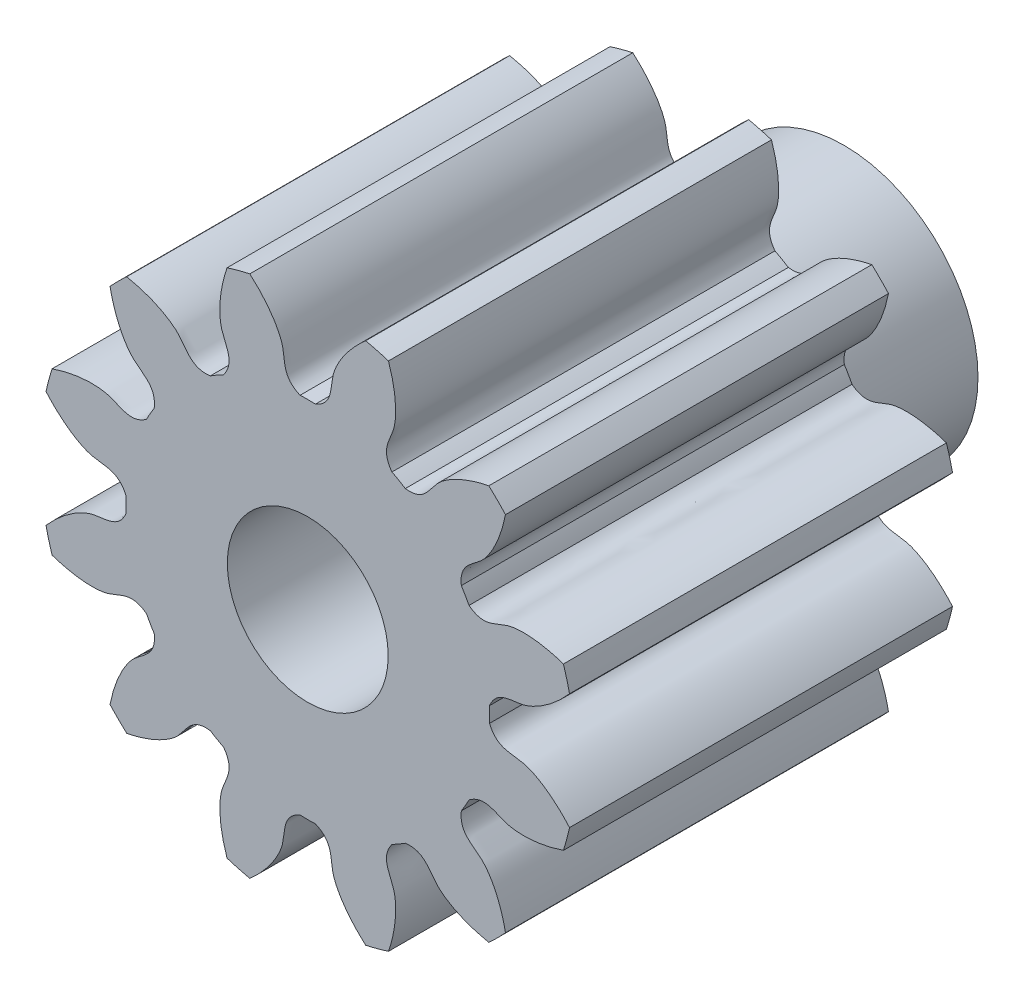
SolidWorks part; units mm, degrees
ref_plane "前视基准面" through (0, 0, 0) normal (0, 0, 1) x (1, 0, 0)
ref_plane "上视基准面" through (0, 0, 0) normal (0, 1, 0) x (1, 0, 0)
ref_plane "右视基准面" through (0, 0, 0) normal (1, 0, 0) x (0, 0, -1)
other "Configuration Table"
sketch "草图1" plane through (0, 0, 0) normal (0, 0, 1) x (1, 0, 0)
  circle A0 centre (0, 0) radius 3.5
extrude "凸台-拉伸1" add sketch "草图1" along normal blind 5
ref_axis "基准轴1" through (0, 0, 5) along (0, 0, -1)
sketch "草图2" plane through (0, 0, 0) normal (0, 0, 1) x (1, 0, 0)
  line L0 (0, 0) -> (0, 3.5) construction
  circle A0 centre (0, 0) radius 3.5 construction
  arc A1 (0.1004, 2.3729) -> (-0.1004, 2.3729) centre (0, 0) ccw
  arc A2 (1.7488, 3.9475) -> (-1.7488, 3.9475) centre (0, 0) ccw
  spline S0 degree 3 poles (0.1004, 2.3729) (0.3404, 2.4747) (0.2872, 2.6724) (0.3381, 2.8447) (0.3413, 2.855) (0.3451, 2.8662) (0.3495, 2.8784) (0.3546, 2.8915) (0.3603, 2.9056) (0.3668, 2.9206) (0.374, 2.9366) (0.3821, 2.9533) (0.3909, 2.971) (0.4007, 2.9894) (0.4114, 3.0086) (0.423, 3.0286) (0.4356, 3.0493) (0.4492, 3.0707) (0.4639, 3.0928) (0.4796, 3.1155) (0.4965, 3.1388) (0.5145, 3.1626) (0.5337, 3.187) (0.554, 3.2119) (0.5756, 3.2372) (0.5985, 3.2629) (0.6226, 3.289) (0.648, 3.3154) (0.6748, 3.342) (0.7028, 3.369) (0.7323, 3.3961) (0.7631, 3.4234) (0.7954, 3.4507) (0.829, 3.4782) (0.8641, 3.5057) (0.9006, 3.5331) (0.9385, 3.5604) (0.978, 3.5877) (1.0189, 3.6147) (1.0613, 3.6416) (1.1052, 3.6681) (1.1506, 3.6944) (1.1975, 3.7203) (1.2459, 3.7457) (1.2958, 3.7707) (1.3472, 3.7952) (1.4001, 3.8191) (1.4546, 3.8424) (1.5105, 3.865) (1.5679, 3.8869) (1.6472, 3.9154) (1.7078, 3.9351) (1.7488, 3.9475) knots 0 0 0 0 0.218015 0.222044 0.226546 0.231522 0.236972 0.242897 0.249295 0.256167 0.263513 0.271332 0.279626 0.288394 0.297636 0.307351 0.317541 0.328204 0.339341 0.350953 0.363038 0.375597 0.38863 0.402137 0.416118 0.430573 0.445502 0.460904 0.476781 0.493132 0.509956 0.527255 0.545027 0.563273 0.581994 0.601188 0.620856 0.640998 0.661614 0.682704 0.704268 0.726305 0.748817 0.771803 0.795262 0.819196 0.843603 0.868484 0.89384 0.919669 0.945972 1 1 1 1
  spline S1 degree 3 poles (-0.1004, 2.3729) (-0.3404, 2.4747) (-0.2872, 2.6724) (-0.3381, 2.8447) (-0.3413, 2.855) (-0.3451, 2.8662) (-0.3495, 2.8784) (-0.3546, 2.8915) (-0.3603, 2.9056) (-0.3668, 2.9206) (-0.374, 2.9366) (-0.3821, 2.9533) (-0.3909, 2.971) (-0.4007, 2.9894) (-0.4114, 3.0086) (-0.423, 3.0286) (-0.4356, 3.0493) (-0.4492, 3.0707) (-0.4639, 3.0928) (-0.4796, 3.1155) (-0.4965, 3.1388) (-0.5145, 3.1626) (-0.5337, 3.187) (-0.554, 3.2119) (-0.5756, 3.2372) (-0.5985, 3.2629) (-0.6226, 3.289) (-0.648, 3.3154) (-0.6748, 3.342) (-0.7028, 3.369) (-0.7323, 3.3961) (-0.7631, 3.4234) (-0.7954, 3.4507) (-0.829, 3.4782) (-0.8641, 3.5057) (-0.9006, 3.5331) (-0.9385, 3.5604) (-0.978, 3.5877) (-1.0189, 3.6147) (-1.0613, 3.6416) (-1.1052, 3.6681) (-1.1506, 3.6944) (-1.1975, 3.7203) (-1.2459, 3.7457) (-1.2958, 3.7707) (-1.3472, 3.7952) (-1.4001, 3.8191) (-1.4546, 3.8424) (-1.5105, 3.865) (-1.5679, 3.8869) (-1.6472, 3.9154) (-1.7078, 3.9351) (-1.7488, 3.9475) knots 0 0 0 0 0.218015 0.222044 0.226546 0.231522 0.236972 0.242897 0.249295 0.256167 0.263513 0.271332 0.279626 0.288394 0.297636 0.307351 0.317541 0.328204 0.339341 0.350953 0.363038 0.375597 0.38863 0.402137 0.416118 0.430573 0.445502 0.460904 0.476781 0.493132 0.509956 0.527255 0.545027 0.563273 0.581994 0.601188 0.620856 0.640998 0.661614 0.682704 0.704268 0.726305 0.748817 0.771803 0.795262 0.819196 0.843603 0.868484 0.89384 0.919669 0.945972 1 1 1 1
extrude "切除-拉伸1" cut sketch "草图2" along normal through all
pattern_circular "阵列(圆周)1" count 12 every 30 about axis through (0, 0, 5) along (0, 0, -1) of "切除-拉伸1"
sketch "草图3" plane through (0, 0, 0) normal (0, 0, 1) x (1, 0, 0)
  circle A0 centre (0, 0) radius 3 construction
  dimension "Dn" = 6
sketch "草图4" plane through (0, 0, 0) normal (0, 0, -1) x (-1, 0, 0)
  circle A0 centre (0, 0) radius 1.75
  dimension "D1" = 3.5
extrude "凸台-拉伸2" add sketch "草图4" along normal blind 2
sketch "草图5" plane through (0, 0, -2) normal (0, 0, -1) x (-1, 0, 0)
  circle A0 centre (0, 0) radius 1.05
  dimension "D1" = 2.1
extrude "切除-拉伸2" cut sketch "草图5" against normal up to next
